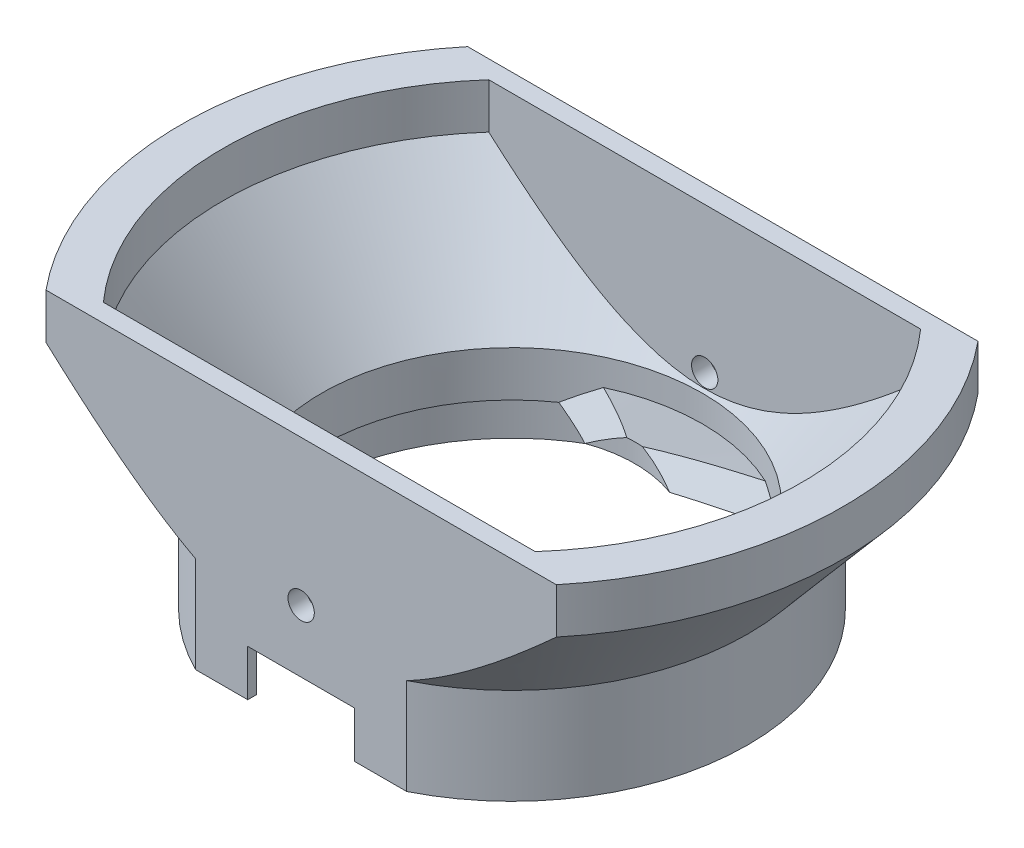
SolidWorks part; units mm, degrees
other "Markup1"
sketch "Sketch12" plane through (-36.5, 26, 23.25) normal (-0.7179, 0.6958, 0.0221) x (0.0006, -0.0311, 0.9995)
ref_plane "Front Plane" through (0, 0, 0) normal (0, 0, 1) x (1, 0, 0)
ref_plane "Top Plane" through (0, 0, 0) normal (0, 1, 0) x (1, 0, 0)
ref_plane "Right Plane" through (0, 0, 0) normal (1, 0, 0) x (0, 0, -1)
sketch "Sketch1" plane through (0, 0, 0) normal (1, 0, 0) x (0, 0, -1)
  line L0 (0, 0) -> (0, 26) construction
  line L1 (-26, 0) -> (-26, 8.5907)
  line L2 (-26, 8.5907) -> (-36.5, 21)
  line L3 (-36.5, 21) -> (-31.9152, 21)
  line L4 (-31.9152, 21) -> (-21, 8.1)
  line L6 (-23.0525, 0) -> (-26, 0)
  line L7 (-23.0525, 0) -> (-23.0525, 3.1)
  line L8 (-36.5, 21) -> (-31.9152, 21)
  line L9 (-36.5, 21) -> (-36.5, 26)
  line L10 (-36.5, 26) -> (-31.9152, 26)
  line L11 (-31.9152, 21) -> (-31.9152, 26)
  line L12 (-23.0525, 3.1) -> (-21, 3.1)
  line L13 (-21, 3.1) -> (-21, 8.1)
  dimension "D1" = 3.5
  dimension "D2" = 26
  dimension "D3" = 23.0525
  dimension "D4" = 36.5
  dimension "D5" = 5
  dimension "D6" = 26
  dimension "D7" = 21
  dimension "D8" = 3.1
  dimension "D9" = 5
revolve "Revolve1" add sketch "Sketch1" angle 360 about L0 region at (0, 10.8751, 26.9281) region at (0, 23.5, 34.2076)
sketch "Sketch2" plane through (0, 0, 0) normal (0, -1, 0) x (1, 0, 0)
  line L1 (-28.1369, -23.25) -> (28.1369, -23.25)
  line L2 (-28.1369, -23.25) -> (-28.1369, -36.5)
  line L3 (-28.1369, -36.5) -> (28.1369, -36.5)
  line L4 (28.1369, -23.25) -> (28.1369, -36.5)
  line L5 (-28.1369, 23.25) -> (28.1369, 23.25)
  line L6 (-28.1369, 23.25) -> (-28.1369, 36.5)
  line L7 (-28.1369, 36.5) -> (28.1369, 36.5)
  line L8 (28.1369, 23.25) -> (28.1369, 36.5)
  circle A0 centre (0, 0) radius 26 construction
  circle A1 centre (0, 0) radius 36.5 construction
  circle A2 centre (0, 0) radius 36.5 construction
  point P5 (0, -23.25)
  dimension "D1" = 23.25
extrude "Cut-Extrude1" cut sketch "Sketch2" against normal through all
sketch "Sketch6" plane through (0, 26, 0) normal (0, 1, 0) x (1, 0, 0)
  line L0 (28.1369, 23.25) -> (-28.1369, 23.25)
  line L1 (-28.1369, 23.25) -> (-28.1369, 21.25)
  line L2 (-28.1369, 21.25) -> (28.1369, 21.25)
  line L3 (28.1369, 21.25) -> (28.1369, 23.25)
  line L5 (-28.1369, -23.25) -> (28.1369, -23.25)
  line L6 (-28.1369, -23.25) -> (-28.1369, -21.25)
  line L7 (-28.1369, -21.25) -> (28.1369, -21.25)
  line L8 (28.1369, -23.25) -> (28.1369, -21.25)
  dimension "D1" = 2
extrude "Boss-Extrude2" add sketch "Sketch6" against normal up to surface (1.0473 mm away) up to face at (0, 15.9992, 0)
sketch "Sketch3" plane through (0, 0, 0) normal (0, -1, 0) x (1, 0, 0)
  line L0 (-11.6378, 23.25) -> (11.6378, 23.25) construction
  line L1 (-5.89, -23.25) -> (5.89, -23.25)
  line L2 (-5.89, -23.25) -> (-5.89, -22.2873)
  line L3 (-5.89, -22.2873) -> (5.89, -22.2873)
  line L4 (5.89, -23.25) -> (5.89, -22.2873)
  line L5 (11.6378, -23.25) -> (-11.6378, -23.25) construction
  line L6 (5.89, 23.25) -> (-5.89, 23.25)
  line L7 (5.89, 23.25) -> (5.89, 22.2873)
  line L8 (5.89, 22.2873) -> (-5.89, 22.2873)
  line L9 (-5.89, 23.25) -> (-5.89, 22.2873)
  circle A0 centre (0, 0) radius 23.0525 construction
  point P6 (0, -22.2873)
  point P16 (0, 22.2873)
  dimension "D1" = 11.78
extrude "Cut-Extrude2" cut sketch "Sketch3" against normal up to surface (3.1 mm away) up to face at (0, 3.1, -21)
ref_plane "Plane1" through (0, 4, 0) normal (0, -1, 0) x (-1, 0, 0)
sketch "Sketch4" plane through (0, 3.1, 0) normal (0, -1, 0) x (-1, 0, 0)
  line L0 (7, 19.799) -> (7, 9.799)
  line L1 (7, 9.799) -> (-7, 9.799)
  line L2 (-7, 9.799) -> (-7, 19.799)
  line L3 (2.7392, -11.7268) -> (-1.0703, -20.9727)
  line L4 (2.7392, -11.7268) -> (-10.2051, -6.3934)
  line L5 (-10.2051, -6.3934) -> (-14.0146, -15.6394)
  line L6 (0, 0) -> (-8, -19.4165) construction
  line L7 (7, 19.799) -> (7, 21.964)
  line L8 (-7, 19.799) -> (-7, 21.964)
  line L9 (-1.0703, -20.9727) -> (-1.8951, -22.9745)
  line L10 (-14.0146, -15.6394) -> (-14.8394, -17.6411)
  circle A0 centre (0, 0) radius 21 construction
  circle A1 centre (0, 0) radius 23.0525
  circle A2 centre (0, 0) radius 23.0525 construction
  point P12 (-3.7329, -9.0601)
  circle M25 centre (0, 0) radius 21
  dimension "D1" = 14
  dimension "D2" = 10
  dimension "D3" = 8
extrude "Boss-Extrude1" [suppressed] add sketch "Sketch4" against normal blind 3 from surface contours L2 L1 L0 M25
mirror "Mirror4" [suppressed] about plane through (0, 0, 0) normal (0, 0, 1)
draft "Draft2" [suppressed] type of draft neutral plane draft angle 50 faces to draft 6 reverse direction yes parameters "D1"=50
fillet "Fillet2" [suppressed] radius 2
sketch "Sketch7" plane through (0, 0, -23.25) normal (0, 0, -1) x (-1, 0, 0)
  line L1 (5.89, 3.1) -> (-5.89, 3.1) construction
  circle A0 centre (0, 9.95) radius 1.45
  dimension "D1" = 2.9
  dimension "D2" = 6.85
extrude "Cut-Extrude3" cut sketch "Sketch7" against normal through all
sketch "Sketch9" plane through (0, 0, 0) normal (1, 0, 0) x (0, 0, -1)
  line L0 (21, 3.1) -> (10.3758, 5.9507)
  line L1 (10.3758, 5.9507) -> (10.8941, 7.8824)
  line L2 (10.8941, 7.8824) -> (21.5183, 5.0317)
  line L3 (21.5183, 5.0317) -> (21, 3.1)
  line L4 (21, 3.1) -> (21, 5.3493) construction
  line L5 (-23.0525, 3.1) -> (23.0525, 3.1) construction
  line L6 (-21, 3.1) -> (21, 3.1) construction
  line L7 (21, 3.1) -> (21, 8.1) construction
  line L8 (21, 3.1) -> (16.054, 3.1) construction
  line L9 (10.8941, 7.8824) -> (21.5183, 8.1)
  line L10 (21.5183, 8.1) -> (21.5183, 5.0317)
  line L11 (21, 8.1) -> (-21, 8.1) construction
  line L12 (0, 0) -> (0, 27.7883) construction
  dimension "D1" = 11
  dimension "D2" = 2
  dimension "D4" = 15.02
revolve "Revolve2" add sketch "Sketch9" angle 70 mid plane about L12 region at (0, 5.4912, -15.9471)
mirror "Mirror3" about plane through (0, 0, 0) normal (0, 0, 1) of "Revolve2"
ref_plane "Plane3" through (0, 0, 0) normal (0.9246, 0, -0.381) x (0.381, 0, 0.9246)
sketch "Sketch13" plane through (0, 0, 0) normal (0, -1, 0) x (1, 0, 0)
  line L0 (-5.89, -23.25) -> (-5.89, -22.2873) construction
  line L1 (-5.89, 22.2873) -> (-5.89, 23.25) construction
  line L2 (-5.89, 23.25) -> (-11.6378, 23.25) construction
  line L3 (-11.6378, -23.25) -> (-5.89, -23.25) construction
  line L4 (5.89, -22.2873) -> (5.89, -23.25) construction
  line L5 (5.89, -23.25) -> (11.6378, -23.25) construction
  line L6 (11.6378, 23.25) -> (5.89, 23.25) construction
  line L7 (5.89, 23.25) -> (5.89, 22.2873) construction
  line L8 (-5.89, -23.25) -> (-5.89, -22.2873)
  line L9 (-5.89, 22.2873) -> (-5.89, 23.25)
  line L10 (-5.89, 23.25) -> (-11.6378, 23.25)
  line L11 (-11.6378, -23.25) -> (-5.89, -23.25)
  line L12 (5.89, -22.2873) -> (5.89, -23.25)
  line L13 (5.89, -23.25) -> (11.6378, -23.25)
  line L14 (11.6378, 23.25) -> (5.89, 23.25)
  line L15 (5.89, 23.25) -> (5.89, 22.2873)
  arc A0 (-5.89, 22.2873) -> (-5.89, -22.2873) centre (0, 0) ccw construction
  arc A1 (-11.6378, 23.25) -> (-11.6378, -23.25) centre (0, 0) ccw construction
  arc A2 (11.6378, -23.25) -> (11.6378, 23.25) centre (0, 0) ccw construction
  arc A3 (5.89, -22.2873) -> (5.89, 22.2873) centre (0, 0) ccw construction
  arc A4 (-5.89, 22.2873) -> (-5.89, -22.2873) centre (0, 0) ccw
  arc A5 (-11.6378, 23.25) -> (-11.6378, -23.25) centre (0, 0) ccw
  arc A6 (11.6378, -23.25) -> (11.6378, 23.25) centre (0, 0) ccw
  arc A7 (5.89, -22.2873) -> (5.89, 22.2873) centre (0, 0) ccw
extrude "Boss-Extrude5" add sketch "Sketch13" along normal blind 2
sketch "Sketch16" plane through (0, 3.1, 0) normal (0, -1, 0) x (1, 0, 0)
  circle A0 centre (0, 0) radius 13.25 construction
  circle A1 centre (0, 0) radius 13.55
  dimension "D1" = 26.5
  dimension "D2" = 0.3
extrude "Cut-Extrude6" cut sketch "Sketch16" against normal through all
sketch "Sketch14" [suppressed] plane through (0, 3.1, 0) normal (0, -1, 0) x (1, 0, 0)
  line L32 (-20.4284, 4.8662) -> (-13.5215, 0.8784)
  line L33 (-19.6822, 7.3221) -> (-13.0864, 3.514)
  line L42 (-7.5215, 11.2707) -> (-14.4284, 15.2585)
  line L43 (-9.5864, 9.5762) -> (-16.1822, 13.3842)
  line L52 (-12.9904, 7.5) -> (-18.1865, 10.5) construction
  line L53 (-16.3843, 5.418) -> (-12.8843, 11.4802) construction
  line L62 (-14.7404, 4.4689) -> (-11.2404, 10.5311)
  line L63 (-6, 20.1246) -> (-6, 12.1492)
  line L72 (-3.5, 20.7063) -> (-3.5, 13.0902)
  line L73 (6, 12.1492) -> (6, 20.1246)
  line L82 (3.5, 13.0902) -> (3.5, 20.7063)
  line L83 (-3.5, 15) -> (3.5, 15)
  line L84 (0, 15) -> (0, 21) construction
  line L85 (-3.5, 16.8982) -> (3.5, 16.8982) construction
  line L86 (14.4284, 15.2585) -> (7.5215, 11.2707)
  line L87 (16.1822, 13.3842) -> (9.5864, 9.5762)
  line L88 (13.5215, 0.8784) -> (20.4284, 4.8662)
  line L89 (13.0864, 3.514) -> (19.6822, 7.3221)
  line L90 (11.2404, 10.5311) -> (14.7404, 4.4689)
  line L91 (12.9904, 7.5) -> (18.1865, 10.5) construction
  line L92 (12.8843, 11.4802) -> (16.3843, 5.418) construction
  line L93 (20.4284, -4.8662) -> (13.5215, -0.8784)
  line L94 (19.6822, -7.3221) -> (13.0864, -3.514)
  line L95 (7.5215, -11.2707) -> (14.4284, -15.2585)
  line L96 (9.5864, -9.5762) -> (16.1822, -13.3842)
  line L97 (14.7404, -4.4689) -> (11.2404, -10.5311)
  line L98 (12.9904, -7.5) -> (18.1865, -10.5) construction
  line L99 (16.3843, -5.418) -> (12.8843, -11.4802) construction
  line L100 (6, -20.1246) -> (6, -12.1492)
  line L101 (3.5, -20.7063) -> (3.5, -13.0902)
  line L102 (-6, -12.1492) -> (-6, -20.1246)
  line L103 (-3.5, -13.0902) -> (-3.5, -20.7063)
  line L104 (3.5, -15) -> (-3.5, -15)
  line L105 (0, -15) -> (0, -21) construction
  line L106 (3.5, -16.8982) -> (-3.5, -16.8982) construction
  line L107 (-14.4284, -15.2585) -> (-7.5215, -11.2707)
  line L108 (-16.1822, -13.3842) -> (-9.5864, -9.5762)
  line L109 (-13.5215, -0.8784) -> (-20.4284, -4.8662)
  line L110 (-13.0864, -3.514) -> (-19.6822, -7.3221)
  line L111 (-11.2404, -10.5311) -> (-14.7404, -4.4689)
  line L112 (-12.9904, -7.5) -> (-18.1865, -10.5) construction
  line L113 (-12.8843, -11.4802) -> (-16.3843, -5.418) construction
  arc A23 (-14.4284, 15.2585) -> (-20.4284, 4.8662) centre (0, 0) ccw construction
  arc A24 (-7.5215, 11.2707) -> (-13.5215, 0.8784) centre (0, 0) ccw construction
  circle A25 centre (0, 0) radius 21 construction
  arc A26 (-7.5215, 11.2707) -> (-13.5215, 0.8784) centre (0, 0) ccw
  arc A27 (-14.4284, 15.2585) -> (-16.1822, 13.3842) centre (0, 0) ccw
  arc A28 (-19.6822, 7.3221) -> (-20.4284, 4.8662) centre (0, 0) ccw
  arc A29 (6, 12.1492) -> (-6, 12.1492) centre (0, 0) ccw
  arc A30 (6, 20.1246) -> (3.5, 20.7063) centre (0, 0) ccw
  arc A31 (-3.5, 20.7063) -> (-6, 20.1246) centre (0, 0) ccw
  arc A32 (13.5215, 0.8784) -> (7.5215, 11.2707) centre (0, 0) ccw
  arc A33 (20.4284, 4.8662) -> (19.6822, 7.3221) centre (0, 0) ccw
  arc A34 (16.1822, 13.3842) -> (14.4284, 15.2585) centre (0, 0) ccw
  arc A35 (7.5215, -11.2707) -> (13.5215, -0.8784) centre (0, 0) ccw
  arc A36 (14.4284, -15.2585) -> (16.1822, -13.3842) centre (0, 0) ccw
  arc A37 (19.6822, -7.3221) -> (20.4284, -4.8662) centre (0, 0) ccw
  arc A38 (-6, -12.1492) -> (6, -12.1492) centre (0, 0) ccw
  arc A39 (-6, -20.1246) -> (-3.5, -20.7063) centre (0, 0) ccw
  arc A40 (3.5, -20.7063) -> (6, -20.1246) centre (0, 0) ccw
  arc A41 (-13.5215, -0.8784) -> (-7.5215, -11.2707) centre (0, 0) ccw
  arc A42 (-20.4284, -4.8662) -> (-19.6822, -7.3221) centre (0, 0) ccw
  arc A43 (-16.1822, -13.3842) -> (-14.4284, -15.2585) centre (0, 0) ccw
  point P19 (-14.6343, 8.4491)
  point P114 (0, 0)
  dimension "D1" = 7
  dimension "D2" = 6
extrude "Cut-Extrude8" [suppressed] cut sketch "Sketch14" against normal through all
draft "Draft11" type of draft neutral plane draft angle 60 faces to draft 4 face at (9.9085, 5.1349, 14.1509) face at (-9.9085, 5.1349, 14.1509) face at (9.9085, 5.1349, -14.1509) face at (-9.9085, 5.1349, -14.1509) neutral plane through (0, 3.1, 0) neutral plane normal (0, -1, 0) reverse direction yes parameters "D1"=60
